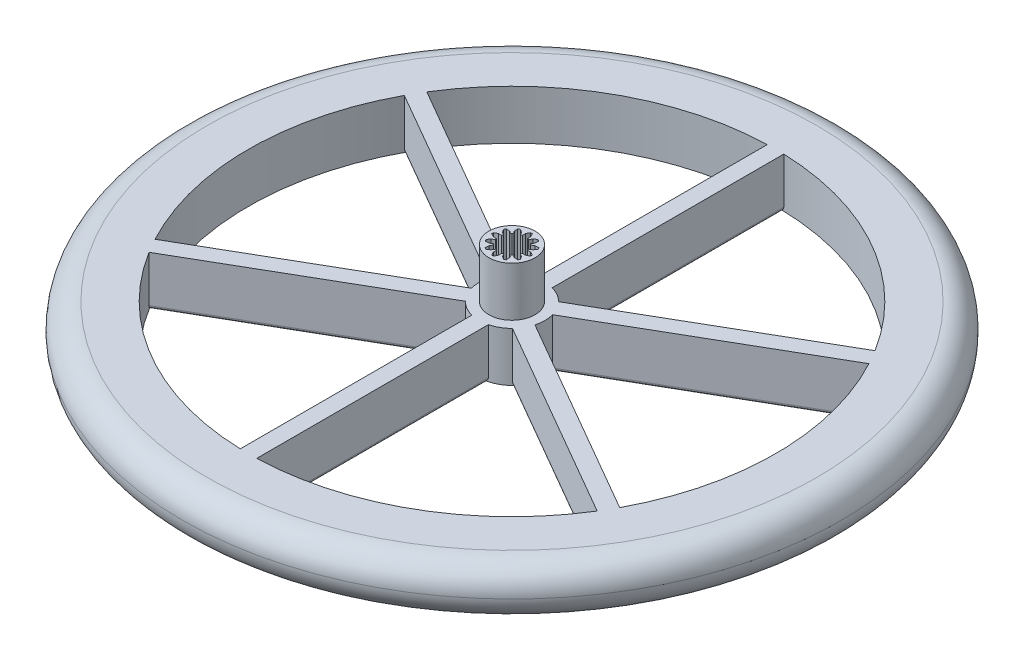
SolidWorks part; units mm, degrees
ref_plane "Front Plane" through (0, 0, 0) normal (0, 0, 1) x (1, 0, 0)
ref_plane "Top Plane" through (0, 0, 0) normal (0, 1, 0) x (1, 0, 0)
ref_plane "Right Plane" through (0, 0, 0) normal (1, 0, 0) x (0, 0, -1)
sketch "Sketch1" plane through (0, 0, 0) normal (0, 1, 0) x (1, 0, 0)
  line L0 (0.8718, 2.3101) -> (0.6334, 1.8971)
  line L2 (-0.4, 2.4365) -> (-0.4, 1.9596)
  line L4 (0.4, 2.4365) -> (0.4, 1.9596)
  line L7 (-0.15, 2.9365) -> (0.15, 2.9365)
  line L9 (-0.15, 2.9365) -> (-0.4, 2.4365)
  line L10 (0.15, 2.9365) -> (0.4, 2.4365)
  line L11 (1.5647, 1.9101) -> (1.3262, 1.4971)
  line L12 (1.3383, 2.6181) -> (1.5981, 2.4681)
  line L13 (1.3383, 2.6181) -> (0.8718, 2.3101)
  line L14 (1.5981, 2.4681) -> (1.5647, 1.9101)
  line L15 (1.9101, 1.5647) -> (1.4971, 1.3262)
  line L16 (2.3101, 0.8718) -> (1.8971, 0.6334)
  line L17 (2.4681, 1.5981) -> (2.6181, 1.3383)
  line L18 (2.4681, 1.5981) -> (1.9101, 1.5647)
  line L19 (2.6181, 1.3383) -> (2.3101, 0.8718)
  line L20 (2.4365, 0.4) -> (1.9596, 0.4)
  line L21 (2.4365, -0.4) -> (1.9596, -0.4)
  line L22 (2.9365, 0.15) -> (2.9365, -0.15)
  line L23 (2.9365, 0.15) -> (2.4365, 0.4)
  line L24 (2.9365, -0.15) -> (2.4365, -0.4)
  line L25 (2.3101, -0.8718) -> (1.8971, -0.6334)
  line L26 (1.9101, -1.5647) -> (1.4971, -1.3262)
  line L27 (2.6181, -1.3383) -> (2.4681, -1.5981)
  line L28 (2.6181, -1.3383) -> (2.3101, -0.8718)
  line L29 (2.4681, -1.5981) -> (1.9101, -1.5647)
  line L30 (1.5647, -1.9101) -> (1.3262, -1.4971)
  line L31 (0.8718, -2.3101) -> (0.6334, -1.8971)
  line L32 (1.5981, -2.4681) -> (1.3383, -2.6181)
  line L33 (1.5981, -2.4681) -> (1.5647, -1.9101)
  line L34 (1.3383, -2.6181) -> (0.8718, -2.3101)
  line L35 (0.4, -2.4365) -> (0.4, -1.9596)
  line L36 (-0.4, -2.4365) -> (-0.4, -1.9596)
  line L37 (0.15, -2.9365) -> (-0.15, -2.9365)
  line L38 (0.15, -2.9365) -> (0.4, -2.4365)
  line L39 (-0.15, -2.9365) -> (-0.4, -2.4365)
  line L40 (-0.8718, -2.3101) -> (-0.6334, -1.8971)
  line L41 (-1.5647, -1.9101) -> (-1.3262, -1.4971)
  line L42 (-1.3383, -2.6181) -> (-1.5981, -2.4681)
  line L43 (-1.3383, -2.6181) -> (-0.8718, -2.3101)
  line L44 (-1.5981, -2.4681) -> (-1.5647, -1.9101)
  line L45 (-1.9101, -1.5647) -> (-1.4971, -1.3262)
  line L46 (-2.3101, -0.8718) -> (-1.8971, -0.6334)
  line L47 (-2.4681, -1.5981) -> (-2.6181, -1.3383)
  line L48 (-2.4681, -1.5981) -> (-1.9101, -1.5647)
  line L49 (-2.6181, -1.3383) -> (-2.3101, -0.8718)
  line L50 (-2.4365, -0.4) -> (-1.9596, -0.4)
  line L51 (-2.4365, 0.4) -> (-1.9596, 0.4)
  line L52 (-2.9365, -0.15) -> (-2.9365, 0.15)
  line L53 (-2.9365, -0.15) -> (-2.4365, -0.4)
  line L54 (-2.9365, 0.15) -> (-2.4365, 0.4)
  line L55 (-2.3101, 0.8718) -> (-1.8971, 0.6334)
  line L56 (-1.9101, 1.5647) -> (-1.4971, 1.3262)
  line L57 (-2.6181, 1.3383) -> (-2.4681, 1.5981)
  line L58 (-2.6181, 1.3383) -> (-2.3101, 0.8718)
  line L59 (-2.4681, 1.5981) -> (-1.9101, 1.5647)
  line L60 (-1.5647, 1.9101) -> (-1.3262, 1.4971)
  line L61 (-0.8718, 2.3101) -> (-0.6334, 1.8971)
  line L62 (-1.5981, 2.4681) -> (-1.3383, 2.6181)
  line L63 (-1.5981, 2.4681) -> (-1.5647, 1.9101)
  line L64 (-1.3383, 2.6181) -> (-0.8718, 2.3101)
  circle A0 centre (0, 0) radius 2
  circle A1 centre (0, 0) radius 3.5
  point P3 (0, 2)
  point P8 (0, 2.4365)
  point P16 (1.2182, 2.1101)
  point P23 (2.1101, 1.2182)
  point P30 (2.4365, 0)
  point P37 (2.1101, -1.2182)
  point P44 (1.2182, -2.1101)
  point P51 (0, -2.4365)
  point P58 (-1.2182, -2.1101)
  point P65 (-2.1101, -1.2182)
  point P72 (-2.4365, 0)
  point P79 (-2.1101, 1.2182)
  point P86 (-1.2182, 2.1101)
  dimension "D1" = 12
  dimension "D2" = 4
  dimension "D5" = 0.3
extrude "Boss-Extrude1" add sketch "Sketch1" along normal blind 7.5 contours A1 A0 L35 L38 L37 L39 L36 L40 L43 L42 L44 L41 L45 L48 L47 L49 L46 L50 L53 L52 L54 L51 L55 L58 L57 L59 L56 L60 L63 L62 L64 L61 L2 L9 L7 L10 L4 L0 L13 L12 L14 L11 region at (-3.401, 0, 0)
sketch "Sketch2" plane through (0, 0, 0) normal (0, -1, 0) x (1, 0, 0)
  line L0 (-1.25, -4.8412) -> (-1.25, -39.9805)
  line L5 (-4.8176, -1.3381) -> (-35.2491, -18.9077)
  line L6 (-3.5676, -3.5031) -> (-33.9991, -21.0728)
  line L7 (-3.5676, 3.5031) -> (-33.9991, 21.0728)
  line L8 (-4.8176, 1.3381) -> (-35.2491, 18.9077)
  line L9 (1.25, -4.8412) -> (1.25, -39.9805)
  line L10 (1.25, 4.8412) -> (1.25, 39.9805)
  line L11 (-1.25, 4.8412) -> (-1.25, 39.9805)
  line L12 (4.8176, 1.3381) -> (35.2491, 18.9077)
  line L13 (3.5676, 3.5031) -> (33.9991, 21.0728)
  line L14 (3.5676, -3.5031) -> (33.9991, -21.0728)
  line L15 (4.8176, -1.3381) -> (35.2491, -18.9077)
  circle A0 centre (0, 0) radius 50
  arc A1 (1.25, -39.9805) -> (33.9991, -21.0728) centre (0, 0) ccw
  arc A2 (1.25, -4.8412) -> (3.5676, -3.5031) centre (0, 0) ccw
  arc A3 (-33.9991, -21.0728) -> (-1.25, -39.9805) centre (0, 0) ccw
  arc A4 (-35.2491, 18.9077) -> (-35.2491, -18.9077) centre (0, 0) ccw
  arc A5 (-1.25, 39.9805) -> (-33.9991, 21.0728) centre (0, 0) ccw
  arc A6 (33.9991, 21.0728) -> (1.25, 39.9805) centre (0, 0) ccw
  arc A7 (35.2491, -18.9077) -> (35.2491, 18.9077) centre (0, 0) ccw
  arc A8 (-1.25, 4.8412) -> (-3.5676, 3.5031) centre (0, 0) ccw
  arc A9 (-4.8176, 1.3381) -> (-4.8176, -1.3381) centre (0, 0) ccw
  arc A10 (-3.5676, -3.5031) -> (-1.25, -4.8412) centre (0, 0) ccw
  arc A11 (4.8176, -1.3381) -> (4.8176, 1.3381) centre (0, 0) ccw
  arc A12 (3.5676, 3.5031) -> (1.25, 4.8412) centre (0, 0) ccw
  dimension "D1" = 6
extrude "Boss-Extrude2" add sketch "Sketch2" along normal blind 7.5
sketch "Sketch3" plane through (0, 0, 0) normal (0, 1, 0) x (1, 0, 0)
  line L0 (0.8718, 2.3101) -> (0.6334, 1.8971)
  line L1 (-0.4, 2.4365) -> (-0.4, 1.9596)
  line L2 (0.4, 2.4365) -> (0.4, 1.9596)
  line L3 (-0.15, 2.9365) -> (0.15, 2.9365)
  line L4 (-0.15, 2.9365) -> (-0.4, 2.4365)
  line L5 (0.15, 2.9365) -> (0.4, 2.4365)
  line L6 (1.5647, 1.9101) -> (1.3262, 1.4971)
  line L7 (1.3383, 2.6181) -> (1.5981, 2.4681)
  line L8 (1.3383, 2.6181) -> (0.8718, 2.3101)
  line L9 (1.5981, 2.4681) -> (1.5647, 1.9101)
  line L10 (1.9101, 1.5647) -> (1.4971, 1.3262)
  line L11 (2.3101, 0.8718) -> (1.8971, 0.6334)
  line L12 (2.4681, 1.5981) -> (2.6181, 1.3383)
  line L13 (2.4681, 1.5981) -> (1.9101, 1.5647)
  line L14 (2.6181, 1.3383) -> (2.3101, 0.8718)
  line L15 (2.4365, 0.4) -> (1.9596, 0.4)
  line L16 (2.4365, -0.4) -> (1.9596, -0.4)
  line L17 (2.9365, 0.15) -> (2.9365, -0.15)
  line L18 (2.9365, 0.15) -> (2.4365, 0.4)
  line L19 (2.9365, -0.15) -> (2.4365, -0.4)
  line L20 (2.3101, -0.8718) -> (1.8971, -0.6334)
  line L21 (1.9101, -1.5647) -> (1.4971, -1.3262)
  line L22 (2.6181, -1.3383) -> (2.4681, -1.5981)
  line L23 (2.6181, -1.3383) -> (2.3101, -0.8718)
  line L24 (2.4681, -1.5981) -> (1.9101, -1.5647)
  line L25 (1.5647, -1.9101) -> (1.3262, -1.4971)
  line L26 (0.8718, -2.3101) -> (0.6334, -1.8971)
  line L27 (1.5981, -2.4681) -> (1.3383, -2.6181)
  line L28 (1.5981, -2.4681) -> (1.5647, -1.9101)
  line L29 (1.3383, -2.6181) -> (0.8718, -2.3101)
  line L30 (0.4, -2.4365) -> (0.4, -1.9596)
  line L31 (-0.4, -2.4365) -> (-0.4, -1.9596)
  line L32 (0.15, -2.9365) -> (-0.15, -2.9365)
  line L33 (0.15, -2.9365) -> (0.4, -2.4365)
  line L34 (-0.15, -2.9365) -> (-0.4, -2.4365)
  line L35 (-0.8718, -2.3101) -> (-0.6334, -1.8971)
  line L36 (-1.5647, -1.9101) -> (-1.3262, -1.4971)
  line L37 (-1.3383, -2.6181) -> (-1.5981, -2.4681)
  line L38 (-1.3383, -2.6181) -> (-0.8718, -2.3101)
  line L39 (-1.5981, -2.4681) -> (-1.5647, -1.9101)
  line L40 (-1.9101, -1.5647) -> (-1.4971, -1.3262)
  line L41 (-2.3101, -0.8718) -> (-1.8971, -0.6334)
  line L42 (-2.4681, -1.5981) -> (-2.6181, -1.3383)
  line L43 (-2.4681, -1.5981) -> (-1.9101, -1.5647)
  line L44 (-2.6181, -1.3383) -> (-2.3101, -0.8718)
  line L45 (-2.4365, -0.4) -> (-1.9596, -0.4)
  line L46 (-2.4365, 0.4) -> (-1.9596, 0.4)
  line L47 (-2.9365, -0.15) -> (-2.9365, 0.15)
  line L48 (-2.9365, -0.15) -> (-2.4365, -0.4)
  line L49 (-2.9365, 0.15) -> (-2.4365, 0.4)
  line L50 (-2.3101, 0.8718) -> (-1.8971, 0.6334)
  line L51 (-1.9101, 1.5647) -> (-1.4971, 1.3262)
  line L52 (-2.6181, 1.3383) -> (-2.4681, 1.5981)
  line L53 (-2.6181, 1.3383) -> (-2.3101, 0.8718)
  line L54 (-2.4681, 1.5981) -> (-1.9101, 1.5647)
  line L55 (-1.5647, 1.9101) -> (-1.3262, 1.4971)
  line L56 (-0.8718, 2.3101) -> (-0.6334, 1.8971)
  line L57 (-1.5981, 2.4681) -> (-1.3383, 2.6181)
  line L58 (-1.5981, 2.4681) -> (-1.5647, 1.9101)
  line L59 (-1.3383, 2.6181) -> (-0.8718, 2.3101)
  circle A0 centre (0, 0) radius 2
  circle A1 centre (0, 0) radius 3.5
  point P2 (0, 2)
  point P7 (0, 2.4365)
  point P14 (1.2182, 2.1101)
  point P21 (2.1101, 1.2182)
  point P28 (2.4365, 0)
  point P35 (2.1101, -1.2182)
  point P42 (1.2182, -2.1101)
  point P49 (0, -2.4365)
  point P56 (-1.2182, -2.1101)
  point P63 (-2.1101, -1.2182)
  point P70 (-2.4365, 0)
  point P77 (-2.1101, 1.2182)
  point P84 (-1.2182, 2.1101)
extrude "Boss-Extrude3" add sketch "Sketch3" along normal blind 1.5 contours A0 L36 L39 L37 L38 L35 | A0 L31 L34 L32 L33 L30 | A0 L26 L29 L27 L28 L25 | A0 | A0 L41 L44 L42 L43 L40 | A0 L46 L49 L47 L48 L45 | A0 L51 L54 L52 L53 L50 | A0 L56 L59 L57 L58 L55 | A0 L2 L5 L3 L4 L1 | A0 L6 L9 L7 L8 L0 | A0 L11 L14 L12 L13 L10 | A0 L16 L19 L17 L18 L15 | A0 L21 L24 L22 L23 L20 region at (1.2004, 0, -2.0791) region at (0, 0, 0) region at (0, 0, -2.4008) region at (2.0791, 0, -1.2004) region at (-1.2004, 0, -2.0791) region at (2.4008, 0, 0) region at (-2.0791, 0, -1.2004) region at (2.0791, 0, 1.2004) region at (-2.4008, 0, 0) region at (1.2004, 0, 2.0791) region at (-2.0791, 0, 1.2004) region at (0, 0, 2.4008) region at (-1.2004, 0, 2.0791)
fillet "Fillet1" radius 3.75 2 edges at (0, -7.5, -50) (0, 0, -50)
fillet "Fillet2" radius 0.5 12 edges at (18.7834, -7.5, -12.288) (-18.7834, -7.5, -12.288) (-20.0334, -7.5, -10.1229) (-20.0334, -7.5, 10.1229) (-18.7834, -7.5, 12.288) (-1.25, -7.5, 22.4108) (1.25, -7.5, 22.4108) (18.7834, -7.5, 12.288) (20.0334, -7.5, 10.1229) (20.0334, -7.5, -10.1229) (1.25, -7.5, -22.4108) (-1.25, -7.5, -22.4108)
